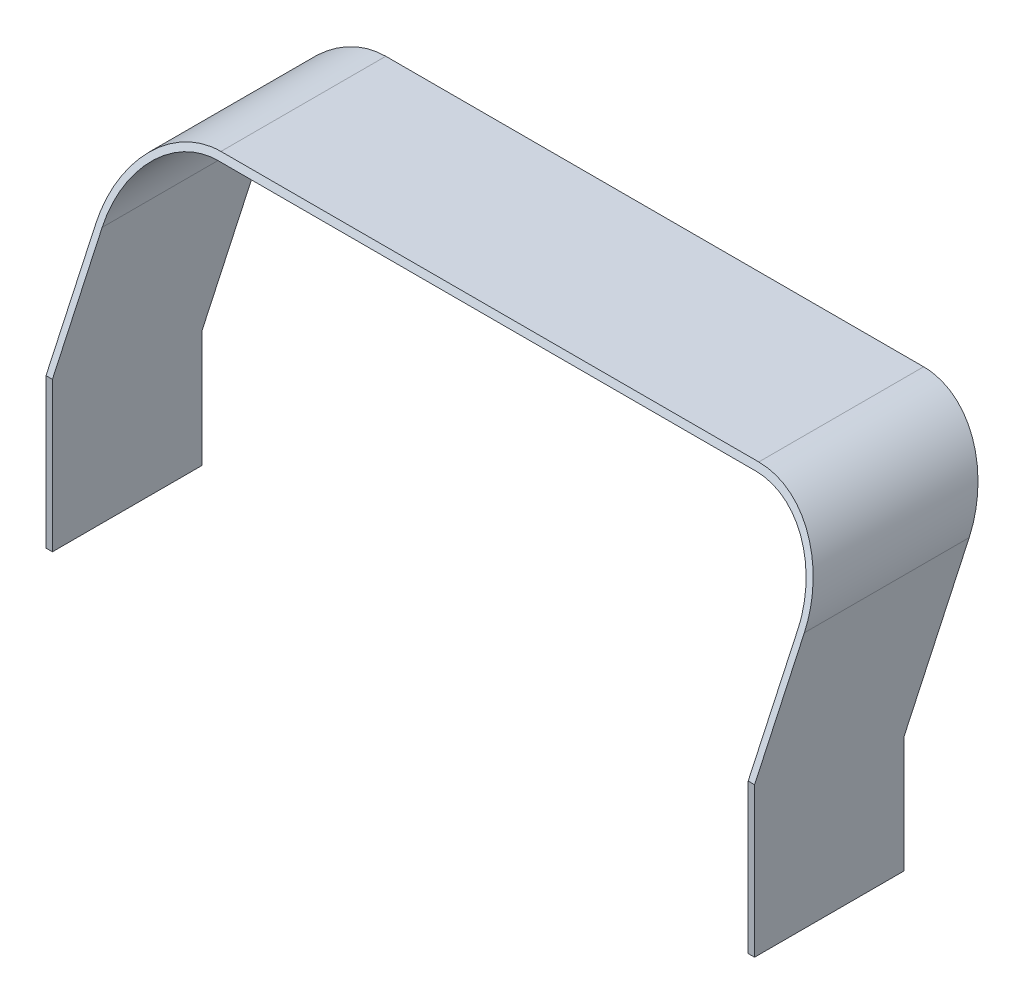
SolidWorks part; units mm, degrees
ref_plane "Front Plane" through (0, 0, 0) normal (0, 0, 1) x (1, 0, 0)
ref_plane "Top Plane" through (0, 0, 0) normal (0, 1, 0) x (1, 0, 0)
ref_plane "Right Plane" through (0, 0, 0) normal (1, 0, 0) x (0, 0, -1)
sketch "Sketch1" plane through (0, 0, 0) normal (0, 0, 1) x (1, 0, 0)
  line L0 (-83, 5) -> (-83, 65)
  line L1 (-63, 85) -> (63, 85)
  line L2 (83, 65) -> (83, 5)
  line L3 (-81.5, 5) -> (-81.5, 65)
  line L4 (-63, 83.5) -> (63, 83.5)
  line L5 (81.5, 65) -> (81.5, 5)
  line L6 (-83, 5) -> (-81.5, 5)
  line L7 (81.5, 5) -> (83, 5)
  arc A0 (63, 85) -> (83, 65) centre (63, 65) cw
  arc A1 (-83, 65) -> (-63, 85) centre (-63, 65) cw
  arc A2 (-81.5, 65) -> (-63, 83.5) centre (-63, 65) cw
  arc A3 (63, 83.5) -> (81.5, 65) centre (63, 65) cw
  dimension "D2" = 20
  dimension "D1" = 80
  dimension "D3" = 1.5
extrude "Boss-Extrude1" add sketch "Sketch1" along normal blind 70
sketch "Sketch2" plane through (-83, 0, 0) normal (-1, 0, 0) x (0, 0, 1)
  line L0 (49.0162, 85) -> (70, 40)
  line L1 (70, 85) -> (0, 85) construction
  line L2 (70, 65) -> (70, 5) construction
  line L3 (10.3979, 85) -> (35, 32.2407)
  line L4 (35, 32.2407) -> (35, 4.8709)
  line L5 (35, 4.8709) -> (0, 4.8709)
  line L6 (0, 0) -> (0, 30) construction
  line L7 (0, 4.8709) -> (0, 85)
  line L8 (0, 85) -> (10.3979, 85)
  line L9 (49.0162, 85) -> (70, 85)
  line L10 (70, 85) -> (70, 40)
  dimension "D1" = 25
  dimension "D2" = 45
  dimension "D3" = 35
  dimension "D4" = 35
extrude "Cut-Extrude1" cut sketch "Sketch2" against normal through all
